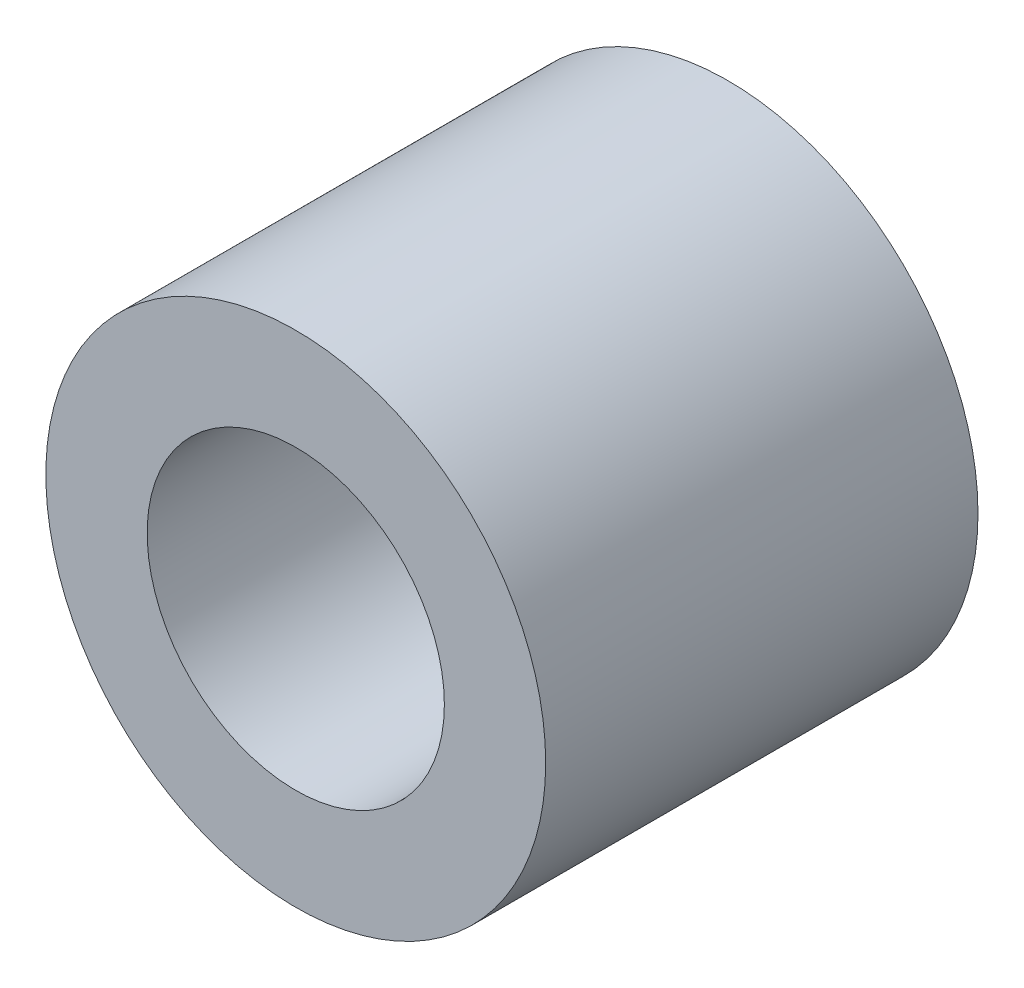
SolidWorks part; units mm, degrees
ref_plane "Front Plane" through (0, 0, 0) normal (0, 0, 1) x (1, 0, 0)
ref_plane "Top Plane" through (0, 0, 0) normal (0, 1, 0) x (1, 0, 0)
ref_plane "Right Plane" through (0, 0, 0) normal (1, 0, 0) x (0, 0, -1)
sketch "Sketch1" plane through (0, 0, 0) normal (0, 0, 1) x (1, 0, 0)
  circle A0 centre (0, 0) radius 5.5
  circle A1 centre (0, 0) radius 9.25
  dimension "D1" = 11
  dimension "18.5" = 18.5
extrude "Boss-Extrude1" add sketch "Sketch1" along normal blind 16
extrude "Boss-Extrude2" add sketch "Sketch1<2>" along normal blind 1.5
sketch "Sketch1<2>" plane through (0, 0, 0) normal (0, 0, 1) x (1, 0, 0) same geometry as "Sketch1"
